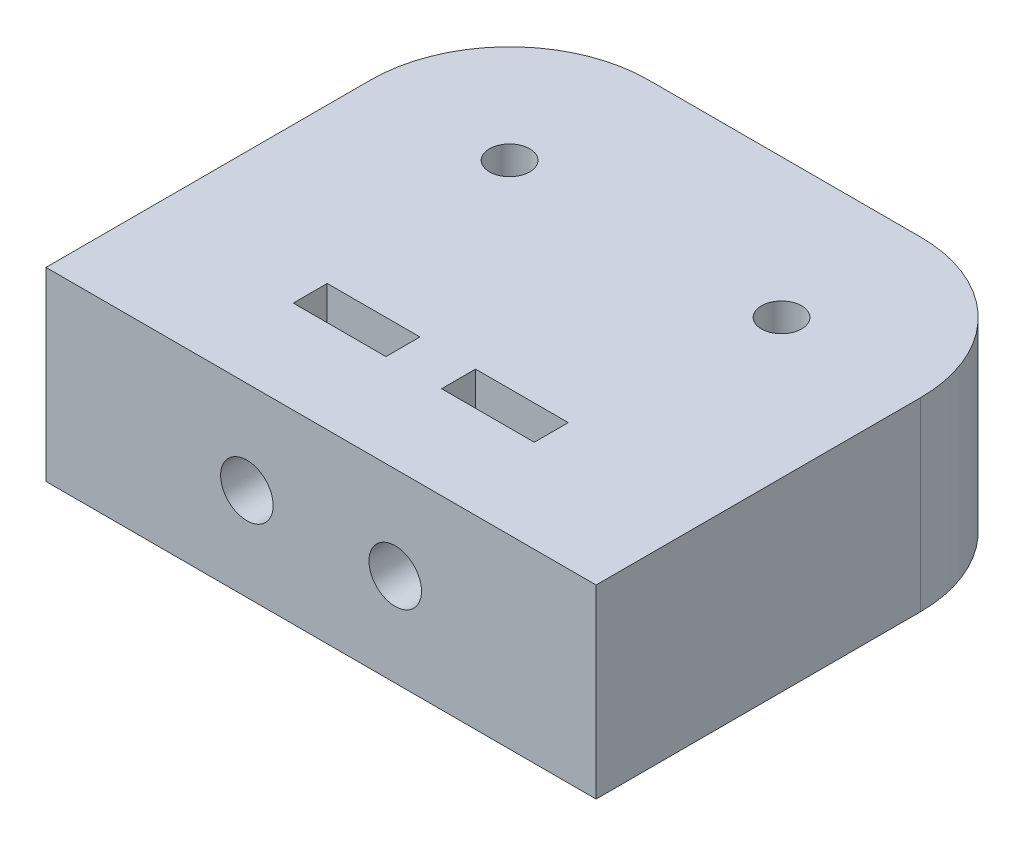
SolidWorks part; units mm, degrees
ref_plane "Front Plane" through (0, 0, 0) normal (0, 0, 1) x (1, 0, 0)
ref_plane "Top Plane" through (0, 0, 0) normal (0, 1, 0) x (1, 0, 0)
ref_plane "Right Plane" through (0, 0, 0) normal (1, 0, 0) x (0, 0, -1)
sketch "Sketch1" plane through (0, 0, 0) normal (0, 1, 0) x (1, 0, 0)
  line L0 (-6.6, 0) -> (6.6, 0) construction
  line L1 (-17.8, 15) -> (0, 15)
  line L2 (-17.8, 15) -> (-17.8, -15)
  line L3 (-17.8, -15) -> (-6.3, -15)
  line L4 (0, 15) -> (0, -15)
  line L5 (-17.8, 15) -> (0, -15) construction
  line L6 (-17.8, -15) -> (0, 15) construction
  line L7 (0, -6.6) -> (0, 6.6) construction
  line L8 (-4.8, -7.9) -> (-4.8, -4) construction
  line L9 (-6.3, -4) -> (-3.3, -4)
  line L10 (-6.3, -4) -> (-6.3, -6.8)
  line L12 (-3.3, -4) -> (-3.3, -6.8)
  line L13 (-6.3, -4) -> (-3.3, -15) construction
  line L14 (-6.3, -15) -> (-3.3, -4) construction
  line L15 (-7.8, -9) -> (-6.3, -9)
  line L16 (-7.8, -9) -> (-7.8, -6.8)
  line L17 (-7.8, -6.8) -> (-6.3, -6.8)
  line L18 (-1.8, -9) -> (-1.8, -6.8)
  line L19 (-7.8, -9) -> (-1.8, -6.8) construction
  line L20 (-7.8, -6.8) -> (-1.8, -9) construction
  line L21 (-3.3, -9) -> (-1.8, -9)
  line L22 (-3.3, -6.8) -> (-1.8, -6.8)
  line L23 (-3.3, -9) -> (-3.3, -15)
  line L24 (-6.3, -9) -> (-6.3, -15)
  line L26 (-3.3, -15) -> (0, -15)
  circle A0 centre (-8.8, 6) radius 1.3
  point P0 (-8.9, 0)
  point P10 (-4.8, -9.5)
  point P15 (-4.8, -7.9)
  dimension "D8" = 2.6
  dimension "D1" = 3
  dimension "D2" = 6
  dimension "D3" = 2.2
  dimension "D4" = 4.8
  dimension "D5" = 11
  dimension "D6" = 6
  dimension "D7" = 10
  dimension "D9" = 9
  dimension "D10" = 9
  dimension "D11" = 30
extrude "Boss-Extrude1" add sketch "Sketch1" along normal blind 12
mirror "Mirror1" about plane through (0, 12, -15) normal (-1, 0, 0) of bodies 101
fillet "Fillet1" radius 9 2 edges at (17.8, 6, -15) (-17.8, 6, -15)
sketch "Sketch2" plane through (0, 0, 0) normal (0, -1, 0) x (1, 0, 0)
  line L0 (6.3, 15) -> (6.3, 9) construction
  line L1 (-6.3, 15) -> (6.3, 15)
  line L2 (-6.3, 15) -> (-6.3, 9)
  line L3 (-6.3, 9) -> (6.3, 9)
  line L4 (6.3, 15) -> (6.3, 9)
  line L6 (-6.3, 4) -> (6.3, 4)
  line L7 (-6.3, 4) -> (-6.3, 6.8)
  line L8 (-6.3, 6.8) -> (6.3, 6.8)
  line L9 (6.3, 4) -> (6.3, 6.8)
extrude "Boss-Extrude2" add sketch "Sketch2" against normal up to surface (12 mm away) up to face at (0, 12, 6.2224)
sketch "Sketch3" plane through (0, 0, 0) normal (0, -1, 0) x (1, 0, 0)
  line L1 (-7.8, 6.8) -> (7.8, 6.8)
  line L2 (-7.8, 6.8) -> (-7.8, 9)
  line L3 (-7.8, 9) -> (7.8, 9)
  line L4 (7.8, 6.8) -> (7.8, 9)
extrude "Boss-Extrude3" add sketch "Sketch3" against normal blind 3
sketch "Sketch4" plane through (0, 0, 15) normal (0, 0, 1) x (1, 0, 0)
  line L0 (-4.8, 6) -> (4.8, 6) construction
  line L1 (0, 0) -> (0, 12) construction
  line L2 (-17.8, 12) -> (17.8, 12) construction
  circle A0 centre (-4.8, 6) radius 1.7
  circle A1 centre (4.8, 6) radius 1.7
  point P9 (0, 6)
  dimension "D1" = 3.4
  dimension "D2" = 9.6
extrude "Cut-Extrude1" cut sketch "Sketch4" against normal blind 12
equation "\"D4@Sketch1\"=9.6/2"
equation "\"D10@Sketch1\"=\"D9@Sketch1\""
equation "\"M3_d\"= \"M3_d_laser@troublemaker.Assembly\""
equation "\"housing_t\"= \"housing_t_glob@troublemaker.Assembly\""
equation "\"D1@Boss-Extrude1\"=12"
equation "\"D1@Sketch1\"=\"M3_d\""
equation "\"M3_nut_m\"= \"M3_nut_m_glob@troublemaker.Assembly\""
equation "\"M3_nut_s\"= \"M3_nut_s_glob@troublemaker.Assembly\""
equation "\"housing_screws_l\"= \"housing_screws_l_glob@troublemaker.Assembly\""
equation "\"housing_nut_l\"= \"housing_nut_l_glob@troublemaker.Assembly\""
equation "\"D6@Sketch1\"=\"housing_nut_l\""
equation "\"D5@Sketch1\"=\"housing_screws_l\""
equation "\"D3@Sketch1\"=\"M3_nut_m\""
